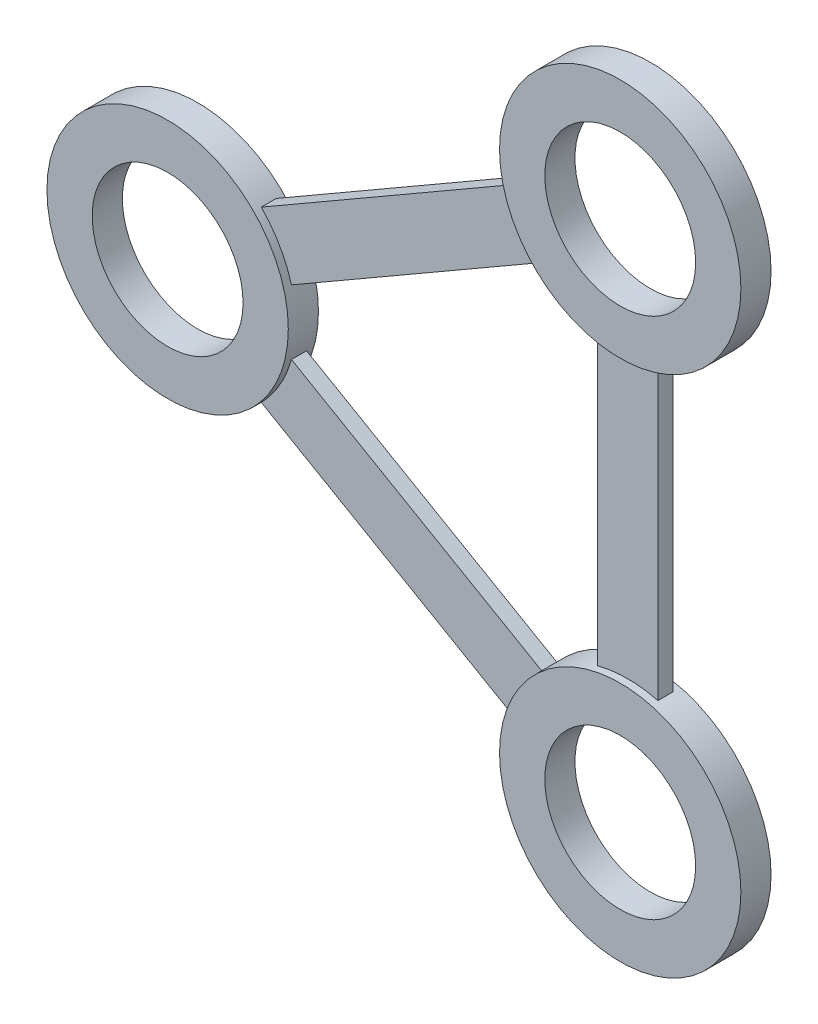
SolidWorks part; units mm, degrees
ref_plane "Front Plane" through (0, 0, 0) normal (0, 0, 1) x (1, 0, 0)
ref_plane "Top Plane" through (0, 0, 0) normal (0, 1, 0) x (1, 0, 0)
ref_plane "Right Plane" through (0, 0, 0) normal (1, 0, 0) x (0, 0, -1)
sketch "Sketch1" plane through (0, 0, 0) normal (0, 0, 1) x (1, 0, 0)
  line L0 (-170.3784, 0) -> (135.2736, 0) construction
  line L1 (70.8657, 163.2525) -> (70.8657, -150.3546) construction
  line L2 (-26.5923, -86.6) -> (123.9394, -86.6) construction
  line L3 (-79.1343, -150.3546) -> (-79.1343, 129.4573) construction
  line L4 (60.8657, 47.8727) -> (60.8657, -47.8702)
  line L5 (123.9394, 86.6) -> (-12.4246, 86.6) construction
  line L6 (80.8657, 47.8727) -> (80.8657, -47.8702)
  line L7 (-79.1343, 0) -> (70.8657, 86.6025) construction
  line L8 (-79.1343, 0) -> (70.8657, -86.6) construction
  line L9 (-40.5933, 10.7047) -> (42.3247, 58.5774)
  line L10 (-50.5933, 28.0252) -> (32.3247, 75.8979)
  line L11 (-50.5929, -28.0248) -> (32.3245, -75.8958)
  line L12 (-40.5931, -10.7042) -> (42.3243, -58.5752)
  circle A0 centre (-79.1343, 0) radius 40
  circle A1 centre (-79.1343, 0) radius 25
  circle A2 centre (70.8657, -86.6) radius 25
  circle A3 centre (70.8657, -86.6) radius 40
  circle A4 centre (70.8657, 86.6025) radius 40
  circle A5 centre (70.8657, 86.6025) radius 25
  dimension "D4" = 80
  dimension "D5" = 50
  dimension "D6" = 50
  dimension "D7" = 80
  dimension "D8" = 80
  dimension "D9" = 50
  dimension "D1" = 86.6
  dimension "D2" = 86.6
  dimension "D3" = 150
  dimension "D10" = 10
  dimension "D11" = 10
  dimension "D12" = 20
extrude "Boss-Extrude1" add sketch "Sketch1" along normal mid plane 5 contours A4 L10 A0 L9 | A3 L12 A0 L11 | A4 L4 A3 L6 region at (70.8657, 0.0013, 0) region at (-4.1343, 43.3013, 0) region at (-4.1343, -43.3, 0)
extrude "Boss-Extrude2" add sketch "Sketch1<3>" along normal mid plane 10 contours A0 A1 | A4 A5 | A3 A2 region at (51.4314, 52.9413, 0) region at (70.8657, -47.7314, 0) region at (-40.6217, 5.249, 0)
sketch "Sketch1<3>" plane through (0, 0, 0) normal (0, 0, 1) x (1, 0, 0) same geometry as "Sketch1"
